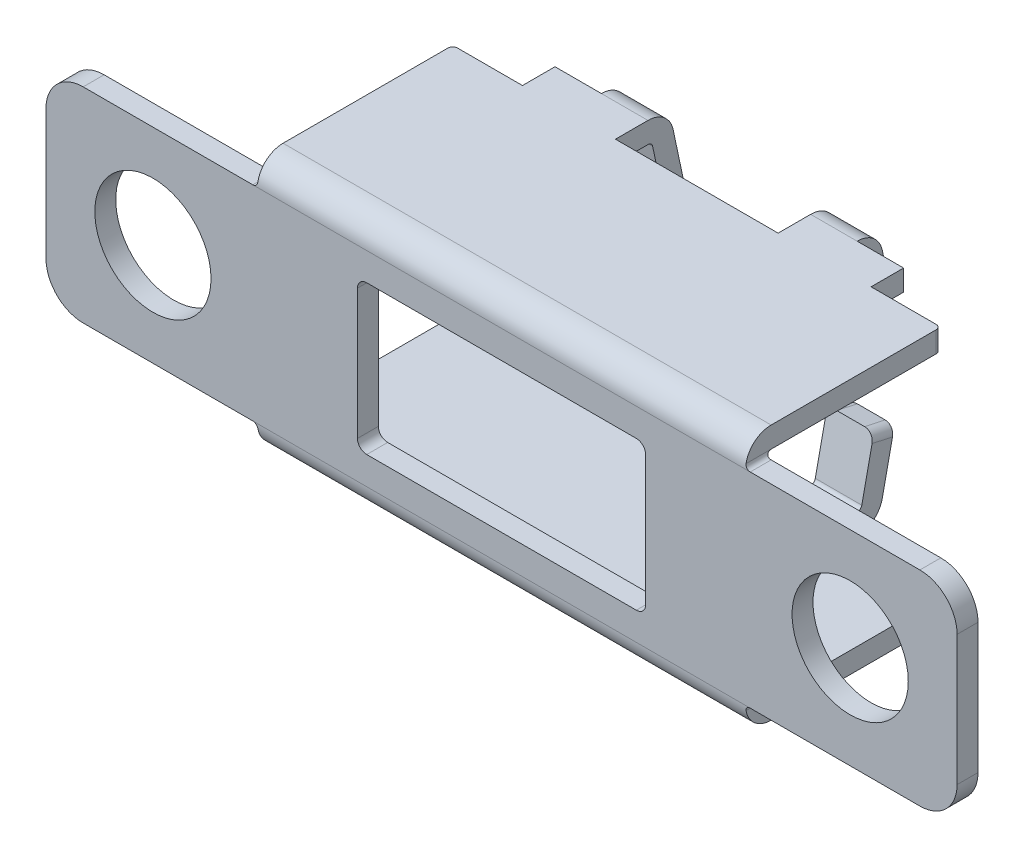
SolidWorks part; units mm, degrees
ref_plane "前视基准面" through (0, 0, 0) normal (0, 0, 1) x (1, 0, 0)
ref_plane "上视基准面" through (0, 0, 0) normal (0, 1, 0) x (1, 0, 0)
ref_plane "右视基准面" through (0, 0, 0) normal (1, 0, 0) x (0, 0, -1)
sketch "草图1" plane through (0, 0, 0) normal (0, 0, 1) x (1, 0, 0)
  line L0 (-7.5, 0) -> (7.5, 0) construction
  line L1 (3.1, -1.6) -> (-3.1, -1.6)
  line L2 (3.1, -1.6) -> (3.1, 1.6)
  line L3 (3.1, 1.6) -> (-3.1, 1.6)
  line L4 (-3.1, -1.6) -> (-3.1, 1.6)
  line L5 (3.1, -1.6) -> (-3.1, 1.6) construction
  line L6 (3.1, 1.6) -> (-3.1, -1.6) construction
  line L7 (9, -2.2) -> (-9, -2.2)
  line L8 (9.8, -1.4) -> (9.8, 1.4)
  line L9 (9, 2.2) -> (-9, 2.2)
  line L10 (-9.8, -1.4) -> (-9.8, 1.4)
  line L11 (9.8, -2.2) -> (-9.8, 2.2) construction
  line L12 (9.8, 2.2) -> (-9.8, -2.2) construction
  circle A1 centre (7.5, 0) radius 1.25
  circle A2 centre (-7.5, 0) radius 1.25
  arc A3 (9.8, 1.4) -> (9, 2.2) centre (9, 1.4) ccw
  arc A4 (9, -2.2) -> (9.8, -1.4) centre (9, -1.4) ccw
  arc A5 (-9, -2.2) -> (-9.8, -1.4) centre (-9, -1.4) cw
  arc A6 (-9, 2.2) -> (-9.8, 1.4) centre (-9, 1.4) ccw
  point P0 (0, 0)
  point P5 (0, 0)
  point P16 (0, 0)
  dimension "D5" = 15
  dimension "D6" = 2.5
  dimension "D7" = 0.8
  dimension "D1" = 3.2
  dimension "D2" = 6.2
  dimension "D3" = 4.4
  dimension "D4" = 19.6
extrude "凸台-拉伸1" add sketch "草图1" against normal blind 0.45
fillet "圆角1" radius 0.2 4 edges at (-3.1, -1.6, -0.225) (3.1, -1.6, -0.225) (3.1, 1.6, -0.225) (-3.1, 1.6, -0.225)
sketch "草图2" plane through (0, 0, 0) normal (1, 0, 0) x (0, 0, -1)
  line L0 (0.55, 2.75) -> (4.2, 2.75)
  line L1 (4.2, 2.75) -> (4.2, 2.3)
  line L2 (4.2, 2.3) -> (0.55, 2.3)
  line L3 (0, 0) -> (4.2, 0) construction
  line L4 (0, -1.4) -> (0, 1.4) construction
  line L5 (0.45, 2.2) -> (0, 2.2) construction
  line L6 (0.45, 2.2) -> (0, 2.2)
  line L7 (4.2, -2.3) -> (0.55, -2.3)
  line L8 (4.2, -2.75) -> (4.2, -2.3)
  line L9 (0.55, -2.75) -> (4.2, -2.75)
  line L10 (0.45, -2.2) -> (0, -2.2)
  line L11 (0, 2.2) -> (0, 1.4) construction
  arc A0 (0, 2.2) -> (0.55, 2.75) centre (0.55, 2.2) cw
  arc A1 (0.55, 2.3) -> (0.45, 2.2) centre (0.55, 2.2) ccw
  arc A2 (0.55, -2.3) -> (0.45, -2.2) centre (0.55, -2.2) cw
  arc A3 (0, -2.2) -> (0.55, -2.75) centre (0.55, -2.2) ccw
  dimension "D1" = 0.45
  dimension "D2" = 5.5
  dimension "D3" = 4.2
extrude "凸台-拉伸2" add sketch "草图2" along normal mid plane 10.5
fillet "圆角2" radius 0.1 4 edges at (5.25, -2.2, -0.225) (5.25, 2.2, -0.225) (-5.25, 2.2, -0.225) (-5.25, -2.2, -0.225)
sketch "草图3" plane through (0, 0, -4.2) normal (0, 0, -1) x (-1, 0, 0)
  line L0 (-5.25, 2.75) -> (5.25, 2.75) construction
  line L1 (2.75, -2.525) -> (-2.75, -2.525) construction
  line L2 (2.75, -2.525) -> (2.75, 2.525) construction
  line L3 (2.75, 2.525) -> (-2.75, 2.525) construction
  line L4 (-2.75, -2.525) -> (-2.75, 2.525) construction
  line L5 (2.75, -2.525) -> (-2.75, 2.525) construction
  line L6 (2.75, 2.525) -> (-2.75, -2.525) construction
  line L7 (-1.75, 2.3) -> (-3.75, 2.3)
  line L8 (-1.75, 2.3) -> (-1.75, 2.75)
  line L9 (-1.75, 2.75) -> (-3.75, 2.75)
  line L10 (-3.75, 2.3) -> (-3.75, 2.75)
  line L11 (-1.75, 2.3) -> (-3.75, 2.75) construction
  line L12 (-1.75, 2.75) -> (-3.75, 2.3) construction
  line L13 (-5.25, 2.3) -> (5.25, 2.3) construction
  line L14 (-5.25, -2.75) -> (5.25, -2.75) construction
  line L15 (1.75, 2.3) -> (3.75, 2.3)
  line L16 (1.75, 2.3) -> (1.75, 2.75)
  line L17 (1.75, 2.75) -> (3.75, 2.75)
  line L18 (3.75, 2.3) -> (3.75, 2.75)
  line L19 (1.75, 2.3) -> (3.75, 2.75) construction
  line L20 (1.75, 2.75) -> (3.75, 2.3) construction
  line L21 (1.75, -2.3) -> (3.75, -2.3)
  line L22 (1.75, -2.3) -> (1.75, -2.75)
  line L23 (1.75, -2.75) -> (3.75, -2.75)
  line L24 (3.75, -2.3) -> (3.75, -2.75)
  line L25 (1.75, -2.3) -> (3.75, -2.75) construction
  line L26 (1.75, -2.75) -> (3.75, -2.3) construction
  line L28 (-1.75, -2.3) -> (-3.75, -2.3)
  line L29 (-1.75, -2.3) -> (-1.75, -2.75)
  line L30 (-1.75, -2.75) -> (-3.75, -2.75)
  line L31 (-3.75, -2.3) -> (-3.75, -2.75)
  line L32 (-1.75, -2.3) -> (-3.75, -2.75) construction
  line L33 (-1.75, -2.75) -> (-3.75, -2.3) construction
  point P0 (0, 0)
  dimension "D1" = 7.5
  dimension "D2" = 2
extrude "凸台-拉伸3" add sketch "草图3" along normal blind 0.7
fillet "圆角3" radius 0.1 4 edges at (-5.25, -2.525, -4.2) (-5.25, 2.525, -4.2) (5.25, -2.525, -4.2) (5.25, 2.525, -4.2)
sketch "草图4" plane through (1.75, 0, 0) normal (-1, 0, 0) x (0, 0, 1)
  line L1 (-5.2619, 0.9867) -> (-5.7021, 1.0803)
  line L2 (-5.7021, 1.0803) -> (-5.4402, 2.3126)
  line L5 (-4.9, 2.3) -> (-4.9, 2.75)
  line L6 (0, 0) -> (-0.45, 0) construction
  line L7 (0, 1.4) -> (0, -1.4) construction
  line L8 (-0.45, 1.4) -> (-0.45, -1.4) construction
  line L13 (-4.9, 2.3) -> (-4.2, 2.3) construction
  line L14 (-5.2619, 0.9867) -> (-5, 2.219)
  line L16 (0, 1.4) -> (0, 2.2) construction
  line L17 (-5.2619, -0.9867) -> (-5.7021, -1.0803)
  line L18 (-5.7021, -1.0803) -> (-5.4402, -2.3126)
  line L19 (-4.9, -2.3) -> (-4.9, -2.75)
  line L20 (-5.2619, -0.9867) -> (-5, -2.219)
  arc A0 (-5.4402, 2.3126) -> (-4.9, 2.75) centre (-4.9, 2.1978) cw
  arc A1 (-5, 2.219) -> (-4.9, 2.3) centre (-4.9, 2.1978) cw
  arc A4 (-5.4402, -2.3126) -> (-4.9, -2.75) centre (-4.9, -2.1978) ccw
  arc A5 (-5, -2.219) -> (-4.9, -2.3) centre (-4.9, -2.1978) ccw
  dimension "D4" = 5
  dimension "D1" = 1.8
  dimension "D2" = 0.45
  dimension "D3" = 12
extrude "凸台-拉伸4" add sketch "草图4" against normal blind 1
mirror "镜向1" about plane through (0, 0, 0) normal (1, 0, 0) of "凸台-拉伸4"
fillet "圆角4" radius 0.2 8 edges at (-2.75, -1.0335, -5.482) (-1.75, -1.0335, -5.482) (2.75, -1.0335, -5.482) (1.75, -1.0335, -5.482) (-2.75, 1.0335, -5.482) (-1.75, 1.0335, -5.482) (1.75, 1.0335, -5.482) (2.75, 1.0335, -5.482)
